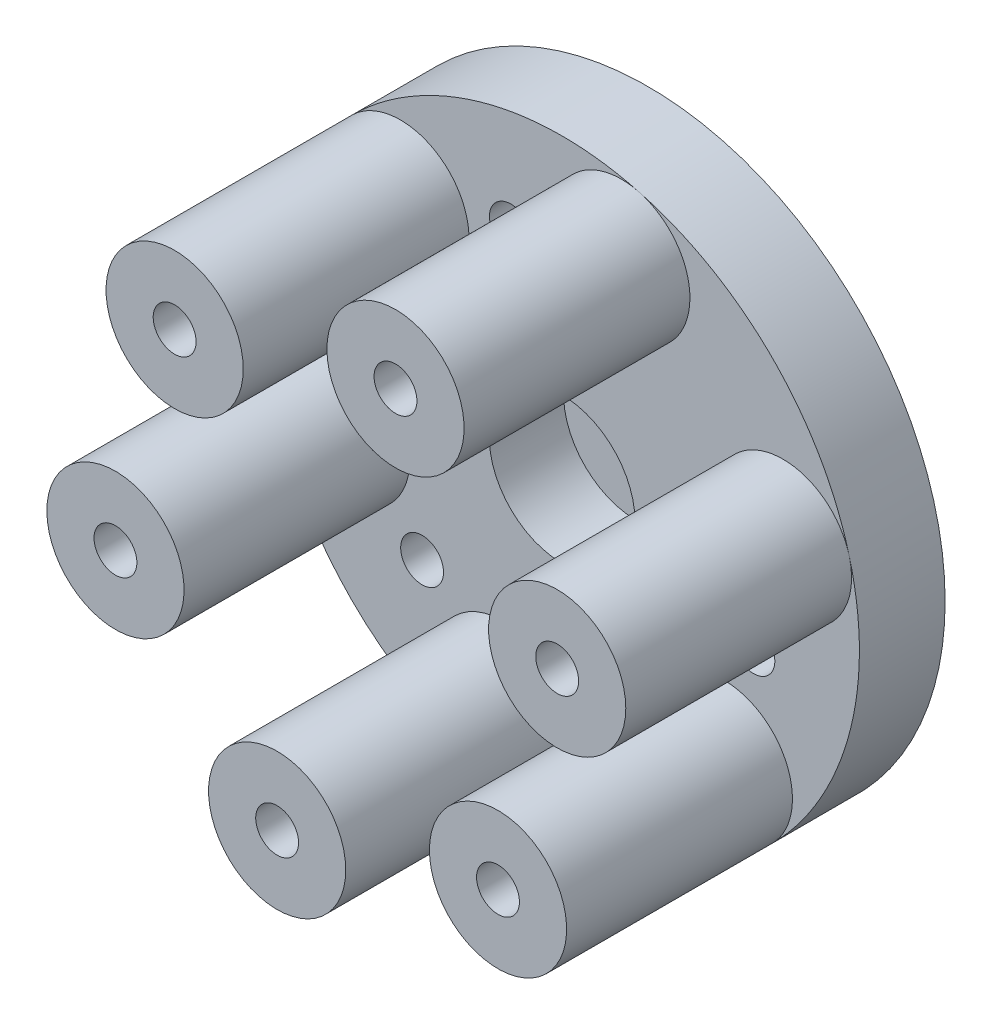
SolidWorks part; units mm, degrees
ref_plane "前视基准面" through (0, 0, 0) normal (0, 0, 1) x (1, 0, 0)
ref_plane "上视基准面" through (0, 0, 0) normal (0, 1, 0) x (1, 0, 0)
ref_plane "右视基准面" through (0, 0, 0) normal (1, 0, 0) x (0, 0, -1)
other "Configuration Table"
sketch "草图1" plane through (0, 0, 0) normal (0, 0, 1) x (1, 0, 0)
  circle A0 centre (0, 0) radius 10.4
  dimension "D1" = 20.8
extrude "凸台-拉伸1" add sketch "草图1" along normal blind 3 contours A0
sketch "草图3" plane through (0, 0, 3) normal (0, 0, 1) x (1, 0, 0)
  line L0 (0, 0) -> (0, 10.0172) construction
  line L1 (-5.6569, 5.6569) -> (0, 0) construction
  circle A0 centre (-5.6569, 5.6569) radius 2.4
  circle A1 centre (-5.6569, 5.6569) radius 0.75
  dimension "D1" = 4.8
  dimension "D3" = 1.5
  dimension "D2" = 8
  dimension "D4" = 45
extrude "凸台-拉伸3" add sketch "草图3" along normal blind 7.9
pattern_circular "阵列(圆周)1" count 6 over 360 about axis through (0, 0, 3) along (0, 0, -1) of "凸台-拉伸3"
sketch "草图4" plane through (0, 0, 3) normal (0, 0, 1) x (1, 0, 0)
  line L2 (-5.6569, 5.6569) -> (2.0706, 7.7274) construction
  circle A0 centre (-1.7932, 6.6921) radius 0.75
  circle A1 centre (-5.6569, 5.6569) radius 0.75 construction
  circle A2 centre (2.0706, 7.7274) radius 0.75 construction
  dimension "D2" = 1.5
extrude "切除-拉伸1" cut sketch "草图4" against normal through all
pattern_circular "阵列(圆周)2" count 3 over 360 about axis through (0, 0, 3) along (0, 0, -1) of "切除-拉伸1" reverse direction yes
sketch "草图5" plane through (0, 0, 3) normal (0, 0, 1) x (1, 0, 0)
  circle A0 centre (0, 0) radius 2.55
  circle A1 centre (0, 0) radius 1.1
  dimension "D1" = 2.2
  dimension "D2" = 5.1
extrude "切除-拉伸2" cut sketch "草图5" against normal through all contours A1
extrude "切除-拉伸3" cut sketch "草图5<4>" against normal blind 2.6
sketch "草图5<4>" plane through (0, 0, 3) normal (0, 0, 1) x (1, 0, 0) same geometry as "草图5"
